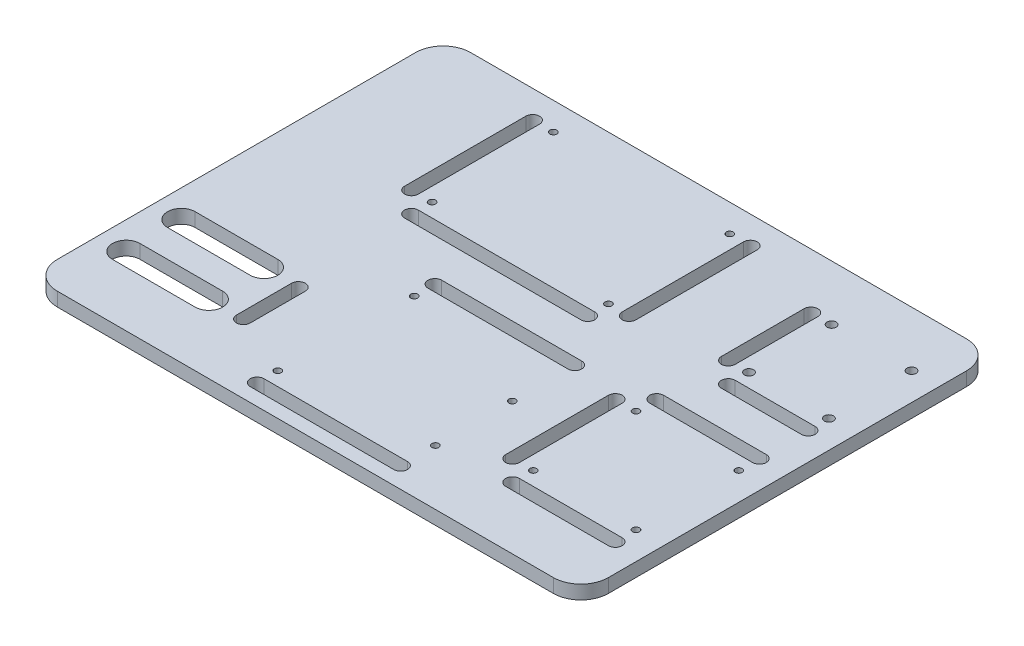
SolidWorks part; units mm, degrees
ref_plane "Front Plane" through (0, 0, 0) normal (0, 0, 1) x (1, 0, 0)
ref_plane "Top Plane" through (0, 0, 0) normal (0, 1, 0) x (1, 0, 0)
ref_plane "Right Plane" through (0, 0, 0) normal (1, 0, 0) x (0, 0, -1)
sketch "Sketch1" plane through (0, 0, 0) normal (0, 1, 0) x (1, 0, 0)
  line L1 (-90, -75) -> (90, -75)
  line L2 (-100, -65) -> (-100, 65)
  line L3 (-90, 75) -> (90, 75)
  line L4 (100, -65) -> (100, 65)
  line L5 (-100, -75) -> (100, 75) construction
  line L6 (-100, 75) -> (100, -75) construction
  arc A0 (90, -75) -> (100, -65) centre (90, -65) ccw
  arc A1 (-90, -75) -> (-100, -65) centre (-90, -65) cw
  arc A2 (-100, 65) -> (-90, 75) centre (-90, 65) cw
  arc A3 (90, 75) -> (100, 65) centre (90, 65) cw
  point P1 (0, 0)
  dimension "D3" = 10
  dimension "D1" = 200
  dimension "D2" = 150
extrude "Boss-Extrude1" add sketch "Sketch1" along normal blind 5 contours L2 A2 L3 A3 L4 A0 L1 A1
hole_wizard "arduino uno holes" positions "Sketch3" profile "Sketch2" tap size "M3x0.5" standard "ANSI Metric" end condition through all
sketch "Sketch3" plane through (0, 5, 0) normal (0, 1, 0) x (1, 0, 0)
  line L0 (-90, -75) -> (90, -75) construction
  line L1 (-100, -65) -> (-100, 65) construction
  point P0 (27.1, -27)
  point P2 (27.1, -54.9)
  point P4 (-23.7, -11.8)
  point P6 (-25, -60)
  dimension "D1" = 27.9
  dimension "D2" = 15.2
  dimension "D3" = 50.8
  dimension "D4" = 1.3
  dimension "D5" = 5.1
  dimension "D6" = 15
  dimension "D7" = 75
sketch "Sketch2" plane through (27.1, 5, 27) normal (1, 0, 0) x (0, 0, 1)
  line L0 (0, 0) -> (0, 5)
  line L1 (0, 5) -> (1.25, 5)
  line L2 (1.25, 5) -> (1.25, 0)
  line L5 (1.25, 0) -> (0, 0)
  line L11 (0, -6.35) -> (0, 107.95) construction
  dimension "Thru Tap Drill Dia." = 2.5
  dimension "Thru Tap Drill Depth" = 5
cosmetic thread "Hole Thread1" parameters "D2"=3
cosmetic thread "Hole Thread2" parameters "D2"=3
cosmetic thread "Hole Thread3" parameters "D2"=3
cosmetic thread "Hole Thread4" parameters "D2"=3
hole_wizard "l298n holes" positions "Sketch16" profile "Sketch17" tap size "M3x0.5" standard "ANSI Metric" end condition through all
sketch "Sketch16" plane through (0, 5, 0) normal (0, 1, 0) x (1, 0, 0)
  line L0 (100, -65) -> (100, 65) construction
  line L1 (-90, -75) -> (90, -75) construction
  point P0 (52.7, -45)
  point P6 (90, -45)
  point P7 (90, -7.7)
  point P8 (52.7, -7.7)
  dimension "D3" = 10
  dimension "D4" = 30
  dimension "D5" = 37.3
  dimension "D6" = 37.3
  dimension "D1" = 2
  dimension "D2" = 2
sketch "Sketch17" plane through (52.7, 5, 45) normal (1, 0, 0) x (0, 0, 1)
  line L0 (0, 0) -> (0, 5)
  line L1 (0, 5) -> (1.25, 5)
  line L2 (1.25, 5) -> (1.25, 0)
  line L5 (1.25, 0) -> (0, 0)
  line L11 (0, -6.35) -> (0, 107.95) construction
  dimension "Thru Tap Drill Dia." = 2.5
  dimension "Thru Tap Drill Depth" = 5
cosmetic thread "Hole Thread25" parameters "D2"=3
cosmetic thread "Hole Thread26" parameters "D2"=3
cosmetic thread "Hole Thread27" parameters "D2"=3
cosmetic thread "Hole Thread28" parameters "D2"=3
hole_wizard "protoboard holes" positions "Sketch20" profile "Sketch21" tap size "M3x0.5" standard "ANSI Metric" end condition through all
sketch "Sketch20" plane through (0, 5, 0) normal (0, 1, 0) x (1, 0, 0)
  line L0 (-90, 75) -> (90, 75) construction
  line L1 (-100, -65) -> (-100, 65) construction
  point P0 (-50, 21)
  point P6 (14, 21)
  point P7 (14, 65)
  point P8 (-50, 65)
  dimension "D3" = 10
  dimension "D4" = 50
  dimension "D5" = 64
  dimension "D6" = 44
  dimension "D1" = 2
  dimension "D2" = 2
sketch "Sketch21" plane through (-50, 5, -21) normal (1, 0, 0) x (0, 0, 1)
  line L0 (0, 0) -> (0, 5)
  line L1 (0, 5) -> (1.25, 5)
  line L2 (1.25, 5) -> (1.25, 0)
  line L5 (1.25, 0) -> (0, 0)
  line L11 (0, -6.35) -> (0, 107.95) construction
  dimension "Thru Tap Drill Dia." = 2.5
  dimension "Thru Tap Drill Depth" = 5
cosmetic thread "Hole Thread37" parameters "D2"=3
cosmetic thread "Hole Thread38" parameters "D2"=3
cosmetic thread "Hole Thread39" parameters "D2"=3
cosmetic thread "Hole Thread40" parameters "D2"=3
hole_wizard "l-bracket holes" positions "Sketch22" profile "Sketch23" tap size "M4x0.7" standard "ANSI Metric" end condition through all
sketch "Sketch22" plane through (0, 5, 0) normal (0, 1, 0) x (1, 0, 0)
  line L0 (-90, 75) -> (90, 75) construction
  line L1 (100, -65) -> (100, 65) construction
  point P12 (61, 55)
  point P19 (90, 55)
  point P20 (90, 25)
  point P21 (61, 25)
  dimension "D1" = 2
  dimension "D2" = 2
  dimension "D3" = 20
  dimension "D4" = 10
sketch "Sketch23" plane through (61, 5, -55) normal (1, 0, 0) x (0, 0, 1)
  line L0 (0, 0) -> (0, 5)
  line L1 (0, 5) -> (1.65, 5)
  line L2 (1.65, 5) -> (1.65, 0)
  line L5 (1.65, 0) -> (0, 0)
  line L11 (0, -6.35) -> (0, 107.95) construction
  dimension "Thru Tap Drill Dia." = 3.3
  dimension "Thru Tap Drill Depth" = 5
cosmetic thread "Hole Thread41" parameters "D2"=4
cosmetic thread "Hole Thread42" parameters "D2"=4
cosmetic thread "Hole Thread43" parameters "D2"=4
cosmetic thread "Hole Thread44" parameters "D2"=4
sketch "Sketch24" plane through (0, 5, 0) normal (0, 1, 0) x (1, 0, 0)
  line L0 (-60, -30) -> (-90, -30) construction
  line L1 (-60, -35) -> (-90, -35)
  line L2 (-60, -25) -> (-90, -25)
  line L3 (-100, -65) -> (-100, 65) construction
  line L4 (-60, -50) -> (-90, -50) construction
  line L5 (-60, -45) -> (-90, -45)
  line L6 (-60, -55) -> (-90, -55)
  line L7 (-90, -75) -> (90, -75) construction
  arc A0 (-60, -35) -> (-60, -25) centre (-60, -30) ccw
  arc A1 (-90, -25) -> (-90, -35) centre (-90, -30) ccw
  arc A2 (-60, -45) -> (-60, -55) centre (-60, -50) cw
  arc A3 (-90, -55) -> (-90, -45) centre (-90, -50) cw
  point P2 (-75, -30)
  point P7 (-95, -30)
  point P8 (-55, -30)
  point P11 (-75, -50)
  dimension "D1" = 10
  dimension "D2" = 40
  dimension "D4" = 20
  dimension "D3" = 5
  dimension "D5" = 10
extrude "power block slots" cut sketch "Sketch24" against normal through all
sketch "Sketch26" plane through (0, 5, 0) normal (0, 1, 0) x (1, 0, 0)
  line L0 (-50, 13.5) -> (14, 13.5) construction
  line L1 (-50, 16) -> (14, 16)
  line L2 (-50, 11) -> (14, 11)
  line L3 (21.5, 65) -> (21.5, 21) construction
  line L4 (24, 65) -> (24, 21)
  line L5 (19, 65) -> (19, 21)
  line L6 (53.5, 55) -> (53.5, 25) construction
  line L7 (56, 55) -> (56, 25)
  line L8 (51, 55) -> (51, 25)
  line L9 (61, 17.5) -> (90, 17.5) construction
  line L10 (61, 20) -> (90, 20)
  line L11 (61, 15) -> (90, 15)
  line L12 (52.7, -0.2) -> (90, -0.2) construction
  line L13 (52.7, 2.3) -> (90, 2.3)
  line L14 (52.7, -2.7) -> (90, -2.7)
  line L15 (45.2, -7.7) -> (45.2, -45) construction
  line L16 (47.7, -7.7) -> (47.7, -45)
  line L17 (42.7, -7.7) -> (42.7, -45)
  line L18 (-25, -67.5) -> (27.1, -67.5) construction
  line L19 (-25, -65) -> (27.1, -65)
  line L20 (-25, -70) -> (27.1, -70)
  line L21 (-47.5, -30) -> (-47.5, -50) construction
  line L22 (-45, -30) -> (-45, -50)
  line L23 (-50, -30) -> (-50, -50)
  line L24 (-23.7, -4.3) -> (27.1, -4.3) construction
  line L25 (-23.7, -1.8) -> (27.1, -1.8)
  line L26 (-23.7, -6.8) -> (27.1, -6.8)
  line L27 (-57.5, 65) -> (-57.5, 21) construction
  line L28 (-55, 65) -> (-55, 21)
  line L29 (-60, 65) -> (-60, 21)
  line L30 (90, -52.5) -> (52.7, -52.5) construction
  line L31 (90, -55) -> (52.7, -55)
  line L32 (90, -50) -> (52.7, -50)
  arc A0 (-50, 16) -> (-50, 11) centre (-50, 13.5) ccw
  arc A1 (14, 11) -> (14, 16) centre (14, 13.5) ccw
  circle A2 centre (14, 21) radius 1.25 construction
  arc A3 (24, 65) -> (19, 65) centre (21.5, 65) ccw
  arc A4 (19, 21) -> (24, 21) centre (21.5, 21) ccw
  arc A5 (56, 55) -> (51, 55) centre (53.5, 55) ccw
  arc A6 (51, 25) -> (56, 25) centre (53.5, 25) ccw
  circle A7 centre (61, 25) radius 1.65 construction
  arc A8 (61, 20) -> (61, 15) centre (61, 17.5) ccw
  arc A9 (90, 15) -> (90, 20) centre (90, 17.5) ccw
  circle A10 centre (90, 25) radius 1.65 construction
  arc A11 (52.7, 2.3) -> (52.7, -2.7) centre (52.7, -0.2) ccw
  arc A12 (90, -2.7) -> (90, 2.3) centre (90, -0.2) ccw
  arc A13 (47.7, -7.7) -> (42.7, -7.7) centre (45.2, -7.7) ccw
  arc A14 (42.7, -45) -> (47.7, -45) centre (45.2, -45) ccw
  circle A15 centre (52.7, -45) radius 1.25 construction
  arc A16 (-25, -65) -> (-25, -70) centre (-25, -67.5) ccw
  arc A17 (27.1, -70) -> (27.1, -65) centre (27.1, -67.5) ccw
  arc A18 (-45, -30) -> (-50, -30) centre (-47.5, -30) ccw
  arc A19 (-50, -50) -> (-45, -50) centre (-47.5, -50) ccw
  circle A20 centre (-25, -60) radius 1.25 construction
  arc A21 (-60, -35) -> (-60, -25) centre (-60, -30) ccw construction
  circle A22 centre (-23.7, -11.8) radius 1.25 construction
  arc A23 (-55, 65) -> (-60, 65) centre (-57.5, 65) ccw
  arc A24 (-60, 21) -> (-55, 21) centre (-57.5, 21) ccw
  circle A25 centre (52.7, -7.7) radius 1.25 construction
  arc A26 (-23.7, -1.8) -> (-23.7, -6.8) centre (-23.7, -4.3) ccw
  arc A27 (27.1, -6.8) -> (27.1, -1.8) centre (27.1, -4.3) ccw
  circle A28 centre (-50, 21) radius 1.25 construction
  arc A29 (90, -55) -> (90, -50) centre (90, -52.5) ccw
  arc A30 (52.7, -50) -> (52.7, -55) centre (52.7, -52.5) ccw
  circle A31 centre (90, -45) radius 1.25 construction
  point P2 (-18, 13.5)
  point P11 (21.5, 43)
  point P18 (53.5, 40)
  point P27 (75.5, 17.5)
  point P36 (71.35, -0.2)
  point P41 (45.2, -26.35)
  point P52 (1.05, -67.5)
  point P59 (-47.5, -40)
  point P72 (1.7, -4.3)
  point P80 (-55, -30)
  point P83 (-57.5, 43)
  point P92 (71.35, -52.5)
  dimension "D1" = 5
  dimension "D2" = 5
  dimension "D3" = 5
  dimension "D4" = 5
  dimension "D5" = 5
  dimension "D6" = 5
  dimension "D7" = 5
  dimension "D8" = 5
  dimension "D9" = 5
  dimension "D10" = 5
  dimension "D11" = 5
  dimension "D12" = 5
  dimension "D15" = 5
  dimension "D16" = 5
  dimension "D17" = 5
  dimension "D18" = 5
  dimension "D13" = 5
  dimension "D14" = 5
  dimension "D19" = 5
  dimension "D20" = 5
  dimension "D21" = 5
  dimension "D22" = 5
extrude "cable management slots" cut sketch "Sketch26" against normal through all
equation "\"w\"= 200"
equation "\"D1@Sketch1\"=\"w\""
equation "\"h\"= 150"
equation "\"D2@Sketch1\"=\"h\""
equation "\"th\"=5"
equation "\"D1@Boss-Extrude1\"=\"th\""
equation "\"D5@Sketch16\"=\"D6@Sketch16\""
equation "\"slot_w\"= 5"
equation "\"D11@Sketch26\"=\"slot_w\""
equation "\"D9@Sketch26\"=\"slot_w\""
equation "\"D5@Sketch26\"=\"slot_w\""
equation "\"D7@Sketch26\"=\"slot_w\""
equation "\"D2@Sketch26\"=\"slot_w\""
equation "\"D3@Sketch26\"=\"slot_w\""
equation "\"D15@Sketch26\"=\"slot_w\""
equation "\"D17@Sketch26\"=\"slot_w\""
equation "\"slot_dist\"= 5"
equation "\"D18@Sketch26\"=\"slot_dist\""
equation "\"D12@Sketch26\"=\"slot_dist\""
equation "\"D10@Sketch26\"=\"slot_dist\""
equation "\"D16@Sketch26\"=\"slot_dist\""
equation "\"D8@Sketch26\"=\"slot_dist\""
equation "\"D6@Sketch26\"=\"slot_dist\""
equation "\"D4@Sketch26\"=\"slot_dist\""
equation "\"D1@Sketch26\"=\"slot_dist\""
equation "\"D14@Sketch26\"=\"slot_dist\""
equation "\"D13@Sketch26\"=\"slot_w\""
equation "\"D19@Sketch26\"=\"slot_w\""
equation "\"D20@Sketch26\"=\"slot_dist\""
equation "\"D21@Sketch26\"=\"slot_w\""
equation "\"D22@Sketch26\"=\"slot_dist\""
